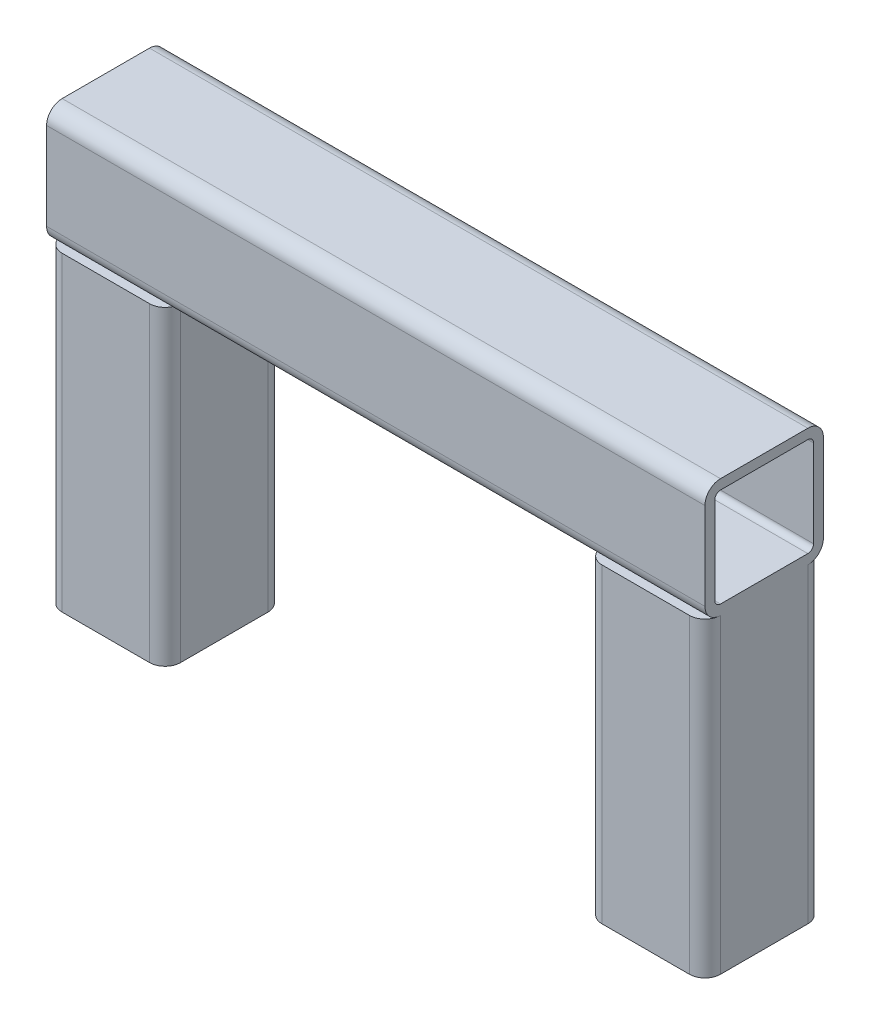
SolidWorks part; units mm, degrees
ref_plane "Front Plane" through (0, 0, 0) normal (0, 0, 1) x (1, 0, 0)
ref_plane "Top Plane" through (0, 0, 0) normal (0, 1, 0) x (1, 0, 0)
ref_plane "Right Plane" through (0, 0, 0) normal (1, 0, 0) x (0, 0, -1)
sketch "Sketch1" plane through (0, 0, 0) normal (0, 1, 0) x (1, 0, 0)
  line L0 (-14.05, 19.05) -> (14.05, 19.05)
  line L1 (19.05, 14.05) -> (19.05, -14.05)
  line L2 (-15.875, 14.05) -> (-15.875, -14.05)
  line L3 (-14.05, -15.875) -> (14.05, -15.875)
  line L4 (14.05, -19.05) -> (-14.05, -19.05)
  line L5 (-19.05, -14.05) -> (-19.05, 14.05)
  line L6 (0, 19.05) -> (0, -19.05) construction
  line L7 (-19.05, 0) -> (19.05, 0) construction
  line L8 (15.875, -14.05) -> (15.875, 14.05)
  line L9 (14.05, 15.875) -> (-14.05, 15.875)
  line L10 (0, 15.875) -> (0, -15.875) construction
  line L11 (-15.875, 0) -> (15.875, 0) construction
  arc A0 (14.05, 19.05) -> (19.05, 14.05) centre (14.05, 14.05) cw
  arc A1 (19.05, -14.05) -> (14.05, -19.05) centre (14.05, -14.05) cw
  arc A2 (-14.05, -19.05) -> (-19.05, -14.05) centre (-14.05, -14.05) cw
  arc A3 (-19.05, 14.05) -> (-14.05, 19.05) centre (-14.05, 14.05) cw
  arc A4 (-15.875, -14.05) -> (-14.05, -15.875) centre (-14.05, -14.05) ccw
  arc A5 (14.05, -15.875) -> (15.875, -14.05) centre (14.05, -14.05) ccw
  arc A6 (15.875, 14.05) -> (14.05, 15.875) centre (14.05, 14.05) ccw
  arc A7 (-14.05, 15.875) -> (-15.875, 14.05) centre (-14.05, 14.05) ccw
  point P33 (0, 0)
  dimension "D1" = 5
  dimension "D2" = 3.175
  dimension "D3" = 38.1
extrude "Boss-Extrude1" add sketch "Sketch1" along normal blind 100
ref_plane "Plane1" through (86.85, 0, 0) normal (1, 0, 0) x (0, 0, -1)
mirror "Mirror2" about plane through (86.85, 0, 0) normal (1, 0, 0) of bodies 101
sketch "Sketch2" plane through (86.85, 0, 0) normal (1, 0, 0) x (0, 0, -1)
  line L0 (-14.05, 138.1) -> (14.05, 138.1)
  line L1 (19.05, 133.1) -> (19.05, 105)
  line L2 (-15.875, 133.1) -> (-15.875, 105)
  line L3 (-14.05, 103.175) -> (14.05, 103.175)
  line L4 (14.05, 100) -> (-14.05, 100)
  line L5 (-19.05, 105) -> (-19.05, 133.1)
  line L6 (0, 138.1) -> (0, 100) construction
  line L7 (-19.05, 119.05) -> (19.05, 119.05) construction
  line L8 (15.875, 105) -> (15.875, 133.1)
  line L9 (14.05, 134.925) -> (-14.05, 134.925)
  line L10 (0, 134.925) -> (0, 103.175) construction
  line L11 (-15.875, 119.05) -> (15.875, 119.05) construction
  line L12 (0, 55) -> (0, -55) construction
  line L13 (14.05, 100) -> (-14.05, 100) construction
  arc A0 (14.05, 138.1) -> (19.05, 133.1) centre (14.05, 133.1) cw
  arc A1 (19.05, 105) -> (14.05, 100) centre (14.05, 105) cw
  arc A2 (-14.05, 100) -> (-19.05, 105) centre (-14.05, 105) cw
  arc A3 (-19.05, 133.1) -> (-14.05, 138.1) centre (-14.05, 133.1) cw
  arc A4 (-15.875, 105) -> (-14.05, 103.175) centre (-14.05, 105) ccw
  arc A5 (14.05, 103.175) -> (15.875, 105) centre (14.05, 105) ccw
  arc A6 (15.875, 133.1) -> (14.05, 134.925) centre (14.05, 133.1) ccw
  arc A7 (-14.05, 134.925) -> (-15.875, 133.1) centre (-14.05, 133.1) ccw
  dimension "D1" = 5
  dimension "D2" = 3.175
  dimension "D3" = 38.1
extrude "Boss-Extrude2" add sketch "Sketch2" along normal up to surface (105.9 mm away) and the other way up to surface (105.9 mm away) up to face at (192.75, 50, 0) other way up to face at (-19.05, 50, 0)
